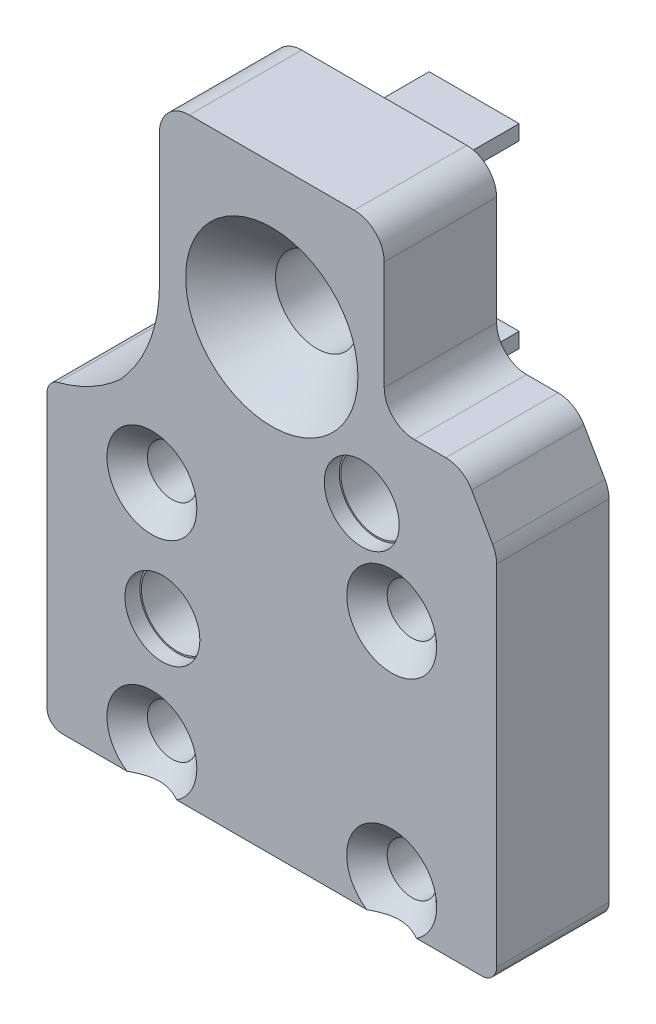
SolidWorks part; units mm, degrees
ref_plane "前视基准面" through (0, 0, 0) normal (0, 0, 1) x (1, 0, 0)
ref_plane "上视基准面" through (0, 0, 0) normal (0, 1, 0) x (1, 0, 0)
ref_plane "右视基准面" through (0, 0, 0) normal (1, 0, 0) x (0, 0, -1)
sketch "草图1" plane through (0, 0, 0) normal (0, 0, 1) x (1, 0, 0)
  line L0 (0, 0) -> (39.64, 0) construction
  line L1 (0, 0) -> (0, 26.4) construction
  line L3 (15, -10) -> (-15, -10)
  line L4 (15, -10) -> (15, 10)
  line L5 (15, 10) -> (-15, 10)
  line L6 (-15, -10) -> (-15, 10)
  point P1 (0, 0)
  dimension "D1" = 20
  dimension "D2" = 30
extrude "凸台-拉伸1" add sketch "草图1" along normal blind 7.5
sketch "草图5" plane through (0, 10, 0) normal (0, 1, 0) x (1, 0, 0)
  line L0 (0, 0) -> (0, -14.2174) construction
  line L1 (15, -7.5) -> (-15, -7.5) construction
  line L2 (7.5, -7.5) -> (-7.5, -7.5)
  line L4 (7.5, 0) -> (-7.5, 0)
  line L5 (-7.5, -7.5) -> (-7.5, 0)
  line L6 (15, 0) -> (-15, 0) construction
  line L7 (7.5, -7.5) -> (7.5, 0)
  point P12 (0, -7.5)
  dimension "D1" = 7.5
extrude "凸台-拉伸2" add sketch "草图5" along normal blind 17.5
sketch "草图6" plane through (0, 0, 0) normal (0, 0, -1) x (-1, 0, 0)
  line L0 (0, 0) -> (0, 28.4964) construction
  line L2 (3, 26) -> (-3, 26)
  line L3 (3, 26) -> (3, 27)
  line L4 (3, 27) -> (-3, 27)
  line L5 (-3, 26) -> (-3, 27)
  line L6 (3, 26) -> (-3, 27) construction
  line L7 (3, 27) -> (-3, 26) construction
  line L8 (-14.4431, 20.5) -> (14.2128, 20.5) construction
  line L9 (3, 15) -> (3, 14)
  line L10 (3, 15) -> (-3, 15)
  line L11 (-3, 15) -> (-3, 14)
  line L12 (3, 14) -> (-3, 14)
  line L13 (-7.5, 27.5) -> (7.5, 27.5) construction
  point P3 (0, 26.5)
  dimension "D1" = 7
  dimension "D2" = 6
  dimension "D3" = 1
  dimension "D4" = 5.5
extrude "凸台-拉伸3" add sketch "草图6" along normal blind 6
sketch "草图10" plane through (0, 0, 7.5) normal (0, 0, 1) x (1, 0, 0)
  line L0 (-7.5, 27.5) -> (7.5, 27.5) construction
  line L1 (7.5, 27.5) -> (7.5, 10) construction
  point P0 (0, 20.5)
  dimension "D1" = 7
  dimension "D2" = 7.5
hole_wizard "M6 内六角花形半沉头螺钉的锥形沉头孔1" positions "草图10" profile "草图9" countersink size "M6" standard "GB" end condition up to next
sketch "草图9" plane through (0, 20.5, 7.5) normal (1, 0, 0) x (0, -1, 0)
  line L0 (0, 0) -> (0, 7.5)
  line L1 (0, 7.5) -> (2.75, 7.5)
  line L2 (2.75, 7.5) -> (2.75, 3)
  line L3 (2.75, 3) -> (5.75, 0)
  line L5 (5.75, 0) -> (0, 0)
  line L6 (-2.75, 3) -> (-5.75, 0) construction
  line L11 (0, -6.35) -> (0, 107.95) construction
  dimension "通孔孔直径" = 5.5
  dimension "通孔孔深度" = 7.5
  dimension "近端锥形沉头孔直径" = 11.5
  dimension "近端锥形沉头孔角度" = 90
sketch "草图11" plane through (0, 0, 7.5) normal (0, 0, 1) x (1, 0, 0)
  line L0 (0, 0) -> (30.091, 0) construction
  line L1 (0, 0) -> (0, 20.5) construction
  circle A0 centre (-7.3, 0) radius 6
  point P1 (-7.3, 0)
  dimension "D1" = 12
  dimension "D2" = 7.3
hole_wizard "Ø4.0mm 暗销孔1" positions "草图11" profile "草图12" hole size "Ø4.0" standard "GB"
sketch "草图12" plane through (-7.3, 0, 7.5) normal (1, 0, 0) x (0, -1, 0)
  line L0 (0, 0) -> (0, 8.9421)
  line L1 (0, 8.9421) -> (2.4, 7.5)
  line L2 (2.4, 7.5) -> (2.4, 0)
  line L5 (2.4, 0) -> (0, 0)
  line L10 (0, 8.9421) -> (-2.4, 7.5) construction
  line L11 (0, -6.35) -> (0, 107.95) construction
  dimension "孔直径" = 4.8
  dimension "孔深度" = 7.5
  dimension "导头角度" = 118
sketch "草图15" plane through (0, 0, 7.5) normal (0, 0, 1) x (1, 0, 0)
  line L0 (7.5, 18.75) -> (12.7628, 18.75)
  line L1 (7.5, 27.5) -> (7.5, 10) construction
  line L2 (12.7628, 18.75) -> (15, 14.8455)
  line L3 (15, 14.8455) -> (15, 10)
  line L4 (7.5, 18.75) -> (7.5, 10)
  line L5 (7.5, 10) -> (15, 10)
  dimension "D1" = 4.5
extrude "凸台-拉伸4" add sketch "草图15" against normal up to surface (7.5 mm away) up to face at (-4.9, 0, 0)
sketch "草图16" plane through (0, 0, 7.5) normal (0, 0, 1) x (1, 0, 0)
  line L0 (0, 0) -> (25.0196, 0) construction
  line L1 (0, 0) -> (0, 20.5) construction
  circle A0 centre (6, 13.3) radius 6
  point P1 (6, 13.3)
  dimension "D1" = 12
  dimension "D3" = 6
  dimension "D2" = 13.3
hole_wizard "Ø4.0mm 暗销孔2" positions "草图16" profile "草图17" hole size "Ø4.0" standard "GB" end condition through all
sketch "草图17" plane through (6, 13.3, 7.5) normal (1, 0, 0) x (0, -1, 0)
  line L0 (0, 0) -> (0, 13.5)
  line L1 (0, 13.5) -> (2.4, 13.5)
  line L2 (2.4, 13.5) -> (2.4, 0)
  line L5 (2.4, 0) -> (0, 0)
  line L11 (0, -6.35) -> (0, 107.95) construction
  dimension "通孔孔直径" = 4.8
  dimension "通孔孔深度" = 13.5
sketch "草图23" plane through (0, 0, 7.5) normal (0, 0, 1) x (1, 0, 0)
  line L0 (0, 0) -> (0, 12.5199) construction
  line L1 (0, 0) -> (10.4168, 0) construction
  line L2 (-7.5, 15) -> (-12.5, 10)
  line L3 (-7.5, 27.5) -> (-7.5, 10) construction
  line L4 (-7.5, 10) -> (-15, 10) construction
  line L5 (-12.5, 10) -> (-7.5, 10)
  line L6 (-7.5, 10) -> (-7.5, 15)
  dimension "D1" = 5
  dimension "D2" = 5
extrude "凸台-拉伸5" add sketch "草图23" against normal up to surface (7.5 mm away) up to face at (8.4, 13.3, 0)
sketch "草图26" plane through (0, 0, 7.5) normal (0, 0, 1) x (1, 0, 0)
  line L0 (0, 0) -> (0, 14.3987) construction
  line L1 (0, 0) -> (14.5369, 0) construction
  circle A0 centre (-8, 7.5) radius 3
  point P1 (-8, 7.5)
  dimension "D1" = 6
  dimension "D2" = 8
  dimension "D3" = 7.5
hole_wizard "M6 内六角花形半沉头螺钉的锥形沉头孔3" positions "草图26" profile "草图27" countersink size "M6" standard "GB"
sketch "草图27" plane through (-8, 7.5, 7.5) normal (1, 0, 0) x (0, -1, 0)
  line L0 (0, 0) -> (0, 8.1914)
  line L1 (0, 8.1914) -> (1.65, 7.2)
  line L2 (1.65, 7.2) -> (1.65, 1.35)
  line L3 (1.65, 1.35) -> (3, 0)
  line L5 (3, 0) -> (0, 0)
  line L6 (-1.65, 1.35) -> (-3, 0) construction
  line L10 (0, 8.1914) -> (-1.65, 7.2) construction
  line L11 (0, -6.35) -> (0, 107.95) construction
  dimension "孔直径" = 3.3
  dimension "孔深度" = 7.2
  dimension "近端锥形沉头孔直径" = 6
  dimension "近端锥形沉头孔角度" = 90
  dimension "导头角度" = 118
mirror "镜向3" about plane through (0, 0, 0) normal (0, 1, 0) of "M6 内六角花形半沉头螺钉的锥形沉头孔3" second plane through (0, 0, 0) second plane normal (1, 0, 0)
fillet "圆角1" radius 10 2 edges at (-12.5, 10, 3.75) (-7.5, 15, 3.75)
fillet "圆角2" radius 1 1 edges at (-15, 10, 3.75)
fillet "圆角4" radius 1 2 edges at (15, -10, 3.75) (-15, -10, 3.75)
fillet "圆角5" radius 2 3 edges at (7.5, 18.75, 3.75) (12.7628, 18.75, 3.75) (15, 14.8455, 3.75)
sketch "草图28" plane through (0, 27.5, 0) normal (0, 1, 0) x (1, 0, 0)
  line L4 (-7.5, 0) -> (-7.5, -7.5)
  line L5 (-7.5, -7.5) -> (7.5, -7.5)
  line L6 (7.5, -7.5) -> (7.5, 0)
  line L7 (7.5, 0) -> (-7.5, 0)
  line L8 (-7.5, 0) -> (-7.5, -7.5)
  line L9 (-7.5, -7.5) -> (7.5, -7.5)
  line L10 (7.5, -7.5) -> (7.5, 0)
  line L11 (7.5, 0) -> (-7.5, 0)
  dimension "D1" = 0
extrude "凸台-拉伸6" add sketch "草图28" along normal blind 2.5
fillet "圆角6" radius 2 2 edges at (7.5, 30, 3.75) (-7.5, 30, 3.75)
sketch "草图29" plane through (0, 0, 7.5) normal (0, 0, 1) x (1, 0, 0)
  circle A2 centre (-7.3, 0) radius 2.5
  circle A3 centre (-7.3, 0) radius 2.5
  circle A5 centre (6, 13.3) radius 2.5
  circle A6 centre (6, 13.3) radius 2.5
  dimension "D2" = 0.1
  dimension "D1" = 0.1
extrude "切除-拉伸1" cut sketch "草图29" against normal blind 1
